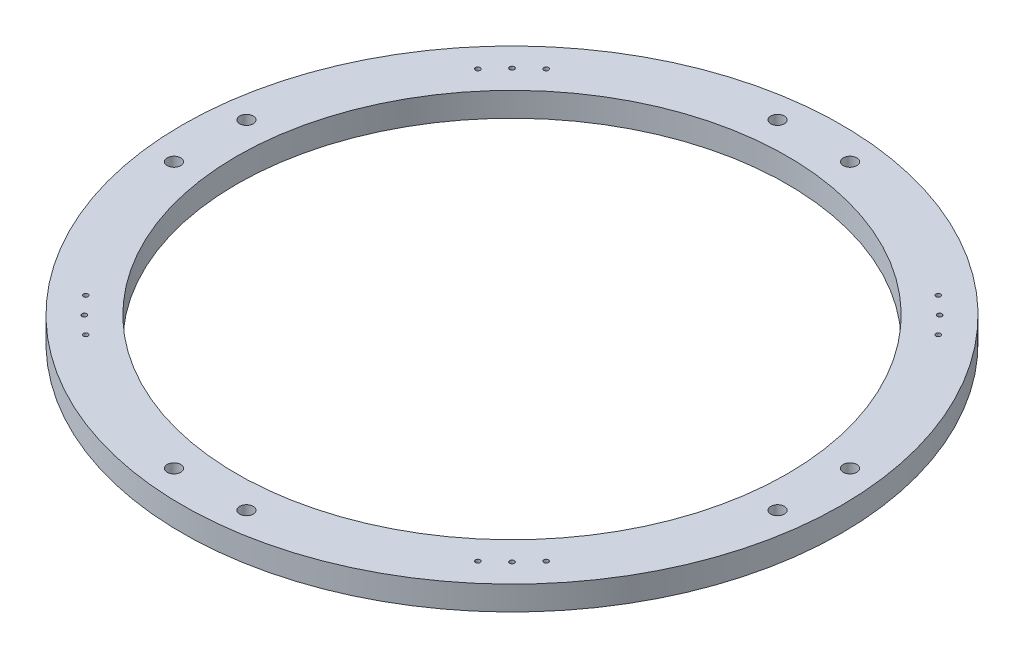
SolidWorks part; units mm, degrees
material "Oak"
ref_plane "Front Plane" through (0, 0, 0) normal (0, 0, 1) x (1, 0, 0)
ref_plane "Top Plane" through (0, 0, 0) normal (0, 1, 0) x (1, 0, 0)
ref_plane "Right Plane" through (0, 0, 0) normal (1, 0, 0) x (0, 0, -1)
sketch "Sketch1" plane through (0, 0, 0) normal (0, 0, 1) x (1, 0, 0)
  line L0 (0, -200000) -> (0, 218797.9879) construction
  line L5 (0, -200000) -> (0, 218797.9879) construction
  line L6 (173.2735, 210.7637) -> (173.2735, 198.0637)
  line L7 (144.6985, 210.7637) -> (173.2735, 210.7637)
  line L8 (173.2735, 198.0637) -> (144.6985, 198.0637)
  line L9 (144.6985, 198.0637) -> (144.6985, 210.7637)
revolve "Revolve1" add sketch "Sketch1" angle 360 about L5
hole_wizard "Tap Drill for M3x0.5 Tap1" positions "Sketch5" profile "Sketch6" hole size "M3x0.5" standard "ANSI Metric" end condition through all
sketch "Sketch5" plane through (0, 210.7637, 0) normal (0, 1, 0) x (1, 0, 0)
  line L0 (0, 0) -> (-112.4201, 112.4201) construction
  point P0 (-112.4201, 112.4201)
  point P3 (-103.0806, 121.0411)
  point P6 (-121.0411, 103.0806)
  dimension "D1" = 158.986
sketch "Sketch6" plane through (-112.4201, 210.7637, -112.4201) normal (1, 0, 0) x (0, 0, 1)
  line L0 (0, 0) -> (0, 12.7)
  line L1 (0, 12.7) -> (1.25, 12.7)
  line L2 (1.25, 12.7) -> (1.25, 0)
  line L5 (1.25, 0) -> (0, 0)
  line L11 (0, -6.35) -> (0, 107.95) construction
  dimension "Thru Hole Dia." = 2.5
  dimension "Thru Hole Depth" = 12.7
sketch "Sketch7" plane through (0, 210.7637, 0) normal (0, 1, 0) x (1, 0, 0)
  line L0 (0, 0) -> (158.6742, 0) construction
  line L1 (158.6742, 19.05) -> (158.6742, -19.05) construction
  line L2 (158.6742, -19.05) -> (0, 0) construction
  line L3 (0, 0) -> (158.6742, 19.05) construction
  circle A0 centre (158.6742, -19.05) radius 3.5719
  circle A1 centre (158.6742, 19.05) radius 3.5719
  point P6 (158.6742, 0)
  dimension "D3" = 7.1437
  dimension "D1" = 38.1
  dimension "D2" = 159.8137
extrude "Cut-Extrude1" cut sketch "Sketch7" against normal through all
pattern_circular "CirPattern1" count 4 over 360 about axis through (0, -200000, 0) along (0, -1, 0) of "Tap Drill for M3x0.5 Tap1", "Cut-Extrude1"
